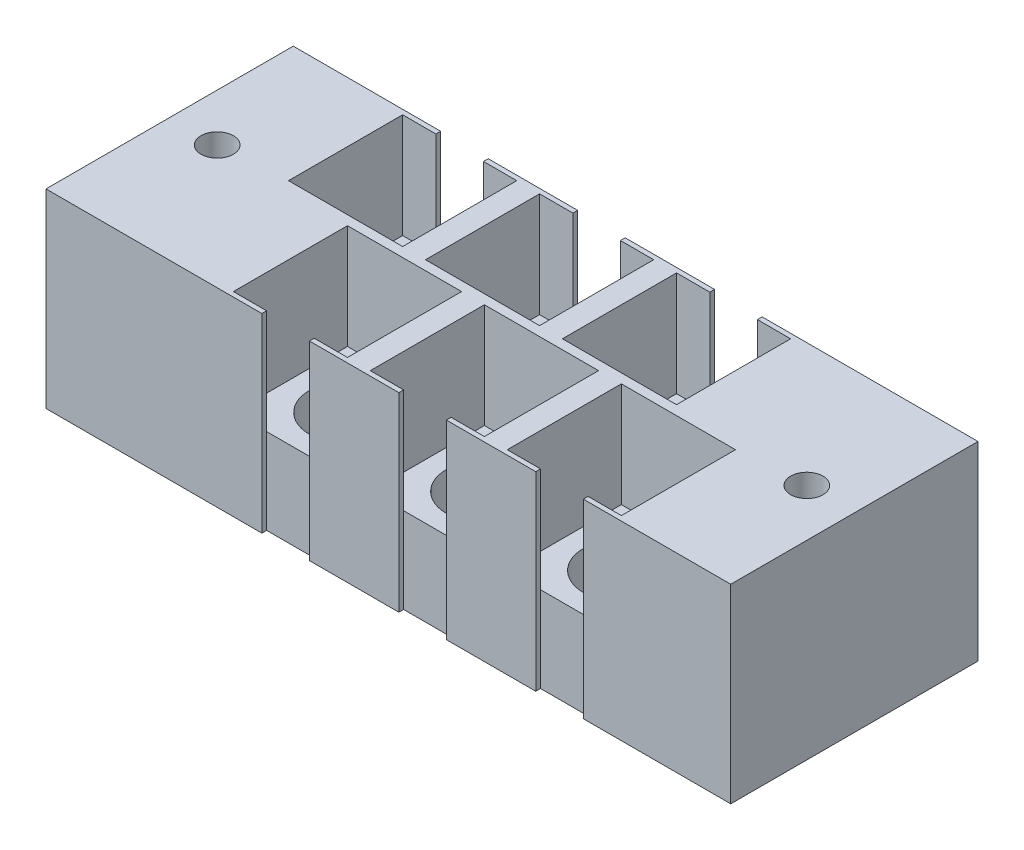
SolidWorks part; units mm, degrees
ref_plane "Front Plane" through (0, 0, 0) normal (0, 0, 1) x (1, 0, 0)
ref_plane "Top Plane" through (0, 0, 0) normal (0, 1, 0) x (1, 0, 0)
ref_plane "Right Plane" through (0, 0, 0) normal (1, 0, 0) x (0, 0, -1)
sketch "Sketch1" plane through (0, 0, 0) normal (0, 1, 0) x (1, 0, 0)
  line L0 (6.1864, -4.1649) -> (7.5864, -4.1649)
  line L1 (21.9864, -4.1649) -> (20.5864, -4.1649)
  line L2 (27.7864, -30.1649) -> (29.1864, -30.1649)
  line L3 (13.3864, -30.1649) -> (14.7864, -30.1649)
  line L4 (-6.8136, -4.1649) -> (-18.3136, -4.1649)
  line L5 (-18.3136, -4.1649) -> (-18.3136, -30.1649)
  line L6 (-18.3136, -30.1649) -> (0.3864, -30.1649)
  line L7 (42.1864, -30.1649) -> (53.6864, -30.1649)
  line L8 (53.6864, -30.1649) -> (53.6864, -4.1649)
  line L9 (53.6864, -4.1649) -> (34.9864, -4.1649)
  line L10 (-18.3136, -17.1649) -> (53.6864, -17.1649) construction
  line L11 (48.6864, -4.1649) -> (48.6864, -30.1649) construction
  line L12 (-13.3136, -4.1649) -> (-13.3136, -30.1649) construction
  circle A0 centre (-13.3136, -17.1649) radius 1.7
  circle A1 centre (48.6864, -17.1649) radius 1.7
  line B0 (34.9864, -17.1649) -> (34.9864, -4.1649)
  line B1 (13.3864, -30.1649) -> (9.3864, -30.1649)
  line B2 (0.8864, -29.6649) -> (12.8864, -29.6649)
  line B3 (13.3864, -30.1649) -> (13.3864, -17.1649)
  line B4 (27.7864, -30.1649) -> (27.7864, -17.1649)
  line B5 (42.1864, -30.1649) -> (42.1864, -17.1649)
  line B6 (0.3864, -17.1649) -> (0.3864, -30.1649)
  line B7 (12.8864, -29.6649) -> (12.8864, -17.6649)
  line B8 (29.1864, -17.1649) -> (29.1864, -30.1649)
  line B9 (21.9864, -4.1649) -> (21.9864, -17.1649)
  line B10 (34.4864, -16.6649) -> (34.4864, -4.6649)
  line B11 (20.0864, -16.6649) -> (20.0864, -4.6649)
  line B12 (6.1864, -17.1649) -> (6.1864, -4.1649)
  line B13 (41.6864, -29.6649) -> (41.6864, -17.6649)
  line B14 (15.2864, -29.6649) -> (27.2864, -29.6649)
  line B15 (29.6864, -17.6649) -> (29.6864, -29.6649)
  line B16 (29.6864, -17.6649) -> (41.6864, -29.6649) construction
  line B17 (15.2864, -17.6649) -> (27.2864, -29.6649) construction
  line B18 (0.8864, -17.6649) -> (12.8864, -29.6649) construction
  line B19 (42.1864, -17.1649) -> (29.1864, -17.1649)
  line B20 (5.6864, -16.6649) -> (5.6864, -4.6649)
  line B21 (15.2864, -17.6649) -> (15.2864, -29.6649)
  line B22 (27.7864, -30.1649) -> (23.7864, -30.1649)
  line B23 (29.1864, -30.1649) -> (33.1864, -30.1649)
  line B24 (42.1864, -30.1649) -> (38.1864, -30.1649)
  line B25 (-6.3136, -10.6649) -> (5.6864, -10.6649) construction
  line B26 (8.0864, -10.6649) -> (20.0864, -10.6649) construction
  line B27 (22.4864, -10.6649) -> (34.4864, -10.6649) construction
  line B28 (0.8864, -23.6649) -> (12.8864, -23.6649) construction
  line B29 (15.2864, -23.6649) -> (27.2864, -23.6649) construction
  line B30 (29.6864, -23.6649) -> (41.6864, -23.6649) construction
  line B31 (-26.4152, -23.6649) -> (52.2342, -23.6649) construction
  line B32 (21.9864, -17.1649) -> (34.9864, -17.1649)
  line B33 (-26.4152, -10.6649) -> (52.2342, -10.6649) construction
  line B34 (28.4864, -16.6649) -> (28.4864, -4.6649) construction
  line B35 (35.6864, -17.6649) -> (35.6864, -29.6649) construction
  line B36 (21.2864, -17.6649) -> (21.2864, -29.6649) construction
  line B37 (14.0864, -16.6649) -> (14.0864, -4.6649) construction
  line B38 (6.8864, -17.6649) -> (6.8864, -29.6649) construction
  line B39 (-0.3136, -16.6649) -> (-0.3136, -4.6649) construction
  line B40 (22.4864, -4.6649) -> (22.4864, -16.6649)
  line B41 (22.4864, -16.6649) -> (34.4864, -16.6649)
  line B42 (34.4864, -4.6649) -> (22.4864, -4.6649)
  line B43 (34.4864, -16.6649) -> (22.4864, -4.6649) construction
  line B44 (34.4864, -4.6649) -> (22.4864, -16.6649) construction
  line B45 (34.9864, -4.1649) -> (30.9864, -4.1649)
  line B46 (21.9864, -4.1649) -> (25.9864, -4.1649)
  line B47 (30.9864, -4.1649) -> (30.9864, -4.6649)
  line B48 (25.9864, -4.1649) -> (25.9864, -4.6649)
  circle B49 centre (28.4864, -10.6649) radius 4
  line B50 (0.8864, -17.6649) -> (0.8864, -29.6649)
  line B51 (12.8864, -17.6649) -> (0.8864, -17.6649)
  line B52 (0.8864, -29.6649) -> (12.8864, -17.6649) construction
  line B53 (13.3864, -17.1649) -> (0.3864, -17.1649)
  line B54 (0.3864, -30.1649) -> (4.3864, -30.1649)
  line B55 (4.3864, -30.1649) -> (4.3864, -29.6649)
  line B56 (9.3864, -30.1649) -> (9.3864, -29.6649)
  circle B57 centre (6.8864, -23.6649) radius 4
  line B58 (27.2864, -29.6649) -> (27.2864, -17.6649)
  line B59 (27.2864, -17.6649) -> (15.2864, -17.6649)
  line B60 (15.2864, -29.6649) -> (27.2864, -17.6649) construction
  line B61 (27.7864, -17.1649) -> (14.7864, -17.1649)
  line B62 (14.7864, -17.1649) -> (14.7864, -30.1649)
  line B63 (14.7864, -30.1649) -> (18.7864, -30.1649)
  line B64 (18.7864, -30.1649) -> (18.7864, -29.6649)
  line B65 (23.7864, -30.1649) -> (23.7864, -29.6649)
  circle B66 centre (21.2864, -23.6649) radius 4
  line B67 (41.6864, -17.6649) -> (29.6864, -17.6649)
  line B68 (29.6864, -29.6649) -> (41.6864, -29.6649)
  line B69 (29.6864, -29.6649) -> (41.6864, -17.6649) construction
  line B70 (33.1864, -30.1649) -> (33.1864, -29.6649)
  line B71 (38.1864, -30.1649) -> (38.1864, -29.6649)
  circle B72 centre (35.6864, -23.6649) radius 4
  line B73 (8.0864, -4.6649) -> (8.0864, -16.6649)
  line B74 (8.0864, -16.6649) -> (20.0864, -16.6649)
  line B75 (20.0864, -4.6649) -> (8.0864, -4.6649)
  line B76 (20.0864, -16.6649) -> (8.0864, -4.6649) construction
  line B77 (20.0864, -4.6649) -> (8.0864, -16.6649) construction
  line B78 (7.5864, -17.1649) -> (20.5864, -17.1649)
  line B79 (20.5864, -17.1649) -> (20.5864, -4.1649)
  line B80 (7.5864, -4.1649) -> (7.5864, -17.1649)
  line B81 (20.5864, -4.1649) -> (16.5864, -4.1649)
  line B82 (7.5864, -4.1649) -> (11.5864, -4.1649)
  line B83 (16.5864, -4.1649) -> (16.5864, -4.6649)
  line B84 (11.5864, -4.1649) -> (11.5864, -4.6649)
  circle B85 centre (14.0864, -10.6649) radius 4
  line B86 (-6.3136, -4.6649) -> (-6.3136, -16.6649)
  line B87 (-6.3136, -16.6649) -> (5.6864, -16.6649)
  line B88 (5.6864, -4.6649) -> (-6.3136, -4.6649)
  line B89 (5.6864, -16.6649) -> (-6.3136, -4.6649) construction
  line B90 (5.6864, -4.6649) -> (-6.3136, -16.6649) construction
  line B91 (-6.8136, -17.1649) -> (6.1864, -17.1649)
  line B92 (-6.8136, -4.1649) -> (-6.8136, -17.1649)
  line B93 (6.1864, -4.1649) -> (2.1864, -4.1649)
  line B94 (-6.8136, -4.1649) -> (-2.8136, -4.1649)
  line B95 (2.1864, -4.1649) -> (2.1864, -4.6649)
  line B96 (-2.8136, -4.1649) -> (-2.8136, -4.6649)
  circle B97 centre (-0.3136, -10.6649) radius 4
  dimension "D5" = 72
  dimension "D1" = 12
  dimension "D2" = 12
  dimension "D3" = 5
  dimension "D4" = 5
  dimension "D6" = 62
  dimension "D7" = 62
sketch_block_instance "Block1-5"
sketch_block "Block1" parameters "D3"=6, "D1"=12, "D2"=12, "D4"=12, "D5"=78.6494, "D6"=78.6494, "D7"=78.6494, "D8"=10.3235, "D9"=14.0261, "D10"=17.7654, "D11"=23.7534, "D12"=22.7743
sketch_block_instance "Block2-2"
sketch_block "Block2" parameters "D1"=12
sketch_block_instance "Block2-3"
sketch_block_instance "Block2-4"
sketch_block_instance "Block2-5"
sketch_block_instance "Block2-6"
sketch_block_instance "Block2-7"
sketch_block_instance "Block3-1"
sketch_block "Block3"
sketch_block_instance "Block4-1"
sketch_block "Block4"
sketch_block_instance "Block5-1"
sketch_block "Block5"
sketch_block_instance "Block6-1"
sketch_block "Block6"
sketch_block_instance "Block7-1"
sketch_block "Block7"
sketch_block_instance "Block8-1"
sketch_block "Block8"
extrude "Boss-Extrude1" add sketch "Sketch1" along normal blind 9 contours B50 B2 B7 B51 B57 | B20 B88 B86 B87 B97 | B11 B75 B73 B74 B85 | B10 B42 B40 B41 B49 | B21 B14 B58 B59 B66 | B15 B68 B13 B67 B72 region at (3.9364, 0, 4.8346) region at (14.0864, 0, 4.8346) region at (2.6364, 0, 29.4952) region at (17.0364, 0, 29.4952) region at (28.4864, 0, 4.8346) region at (31.4364, 0, 29.4952)
extrude "Boss-Extrude2" add sketch "Sketch1<4>" along normal blind 20 contours B92 L4 L5 L6 B6 B91 A0 | B8 B32 B4 L2 | B79 B61 B9 L1 | B78 B3 L3 B62 | B12 B53 B80 L0 | B96 B94 B92 B91 B53 B12 B93 B95 B88 B20 B87 B86 | B56 B1 B3 B53 B6 B54 B55 B2 B50 B51 B7 | B84 B82 B80 B53 B78 B61 B79 B81 B83 B75 B11 B74 B73 | B71 B24 B5 B19 B32 B8 B23 B70 B68 B15 B67 B13 | B48 B46 B9 B32 B0 B45 B47 B42 B10 B41 B40 | B65 B22 B4 B32 B61 B62 B63 B64 B14 B21 B59 B58 | B5 L7 L8 L9 B0 B19 A1 region at (6.8864, 0, 10.6649) region at (6.0025, 0, 10.6649) region at (9.5864, 0, 4.3487) region at (6.8864, 0, 17.3487) region at (-10.2639, 0, 18.7512) region at (14.0864, 0, 23.6649) region at (17.6864, 0, 17.3487) region at (21.2864, 0, 10.6649) region at (22.1702, 0, 10.6649) region at (28.4864, 0, 23.6649) region at (32.0864, 0, 17.3487) region at (45.6367, 0, 15.5785)
sketch "Sketch1<4>" plane through (0, 0, 0) normal (0, 1, 0) x (1, 0, 0) same geometry as "Sketch1"
sketch "Sketch2" plane through (0, 0, 0) normal (0, -1, 0) x (1, 0, 0)
  line L0 (-0.3136, 4.6649) -> (-0.3136, 30.1649) construction
  line L1 (2.1864, 4.6649) -> (-2.8136, 4.6649) construction
  line L2 (-18.3136, 30.1649) -> (4.3864, 30.1649) construction
  line L3 (6.8864, 29.6649) -> (6.8864, 4.1649) construction
  line L4 (4.3864, 29.6649) -> (9.3864, 29.6649) construction
  line L5 (2.1864, 4.1649) -> (11.5864, 4.1649) construction
  line L6 (14.0864, 4.6649) -> (14.0864, 30.1649) construction
  line L7 (16.5864, 4.6649) -> (11.5864, 4.6649) construction
  line L8 (9.3864, 30.1649) -> (18.7864, 30.1649) construction
  line L9 (21.2864, 29.6649) -> (21.2864, 4.1649) construction
  line L10 (18.7864, 29.6649) -> (23.7864, 29.6649) construction
  line L11 (25.9864, 4.1649) -> (16.5864, 4.1649) construction
  line L12 (28.4864, 4.6649) -> (28.4864, 30.1649) construction
  line L13 (30.9864, 4.6649) -> (25.9864, 4.6649) construction
  line L14 (33.1864, 30.1649) -> (23.7864, 30.1649) construction
  line L15 (35.6864, 29.6649) -> (35.6864, 4.1649) construction
  line L16 (33.1864, 29.6649) -> (38.1864, 29.6649) construction
  line L17 (53.6864, 4.1649) -> (30.9864, 4.1649) construction
  line L18 (-0.3136, 17.4149) -> (35.6864, 17.4149) construction
  line L19 (6.8864, 19.6649) -> (-18.3136, 19.6649) construction
  line L20 (-18.3136, 4.1649) -> (-18.3136, 30.1649) construction
  line L21 (-18.3136, 19.6649) -> (53.6864, 19.6649) construction
  line L22 (53.6864, 30.1649) -> (53.6864, 4.1649) construction
  line L23 (-0.3136, 14.6649) -> (-18.3136, 14.6649) construction
  line L24 (-18.3136, 14.6649) -> (53.6864, 14.6649) construction
  line L25 (4.3864, 19.6649) -> (4.3864, 14.6649)
  line L26 (4.3864, 14.6649) -> (2.1864, 14.6649)
  line L27 (2.1864, 14.6649) -> (2.1864, 19.6649)
  line L28 (2.1864, 19.6649) -> (4.3864, 19.6649)
  circle A0 centre (6.8864, 23.6649) radius 4 construction
  circle A1 centre (-0.3136, 10.6649) radius 4 construction
  line B0 (6.8864, 4.6649) -> (6.8864, 30.1649) construction
  line B1 (11.5864, 19.6649) -> (11.5864, 14.6649)
  line B2 (11.5864, 14.6649) -> (9.3864, 14.6649)
  line B3 (9.3864, 14.6649) -> (9.3864, 19.6649)
  line B4 (9.3864, 19.6649) -> (11.5864, 19.6649)
  line B5 (18.7864, 19.6649) -> (18.7864, 14.6649)
  line B6 (18.7864, 14.6649) -> (16.5864, 14.6649)
  line B7 (16.5864, 14.6649) -> (16.5864, 19.6649)
  line B8 (16.5864, 19.6649) -> (18.7864, 19.6649)
  line B9 (25.9864, 19.6649) -> (25.9864, 14.6649)
  line B10 (25.9864, 14.6649) -> (23.7864, 14.6649)
  line B11 (23.7864, 14.6649) -> (23.7864, 19.6649)
  line B12 (23.7864, 19.6649) -> (25.9864, 19.6649)
  line B13 (33.1864, 19.6649) -> (33.1864, 14.6649)
  line B14 (33.1864, 14.6649) -> (30.9864, 14.6649)
  line B15 (30.9864, 14.6649) -> (30.9864, 19.6649)
  line B16 (30.9864, 19.6649) -> (33.1864, 19.6649)
  dimension "D1" = 2.5
  dimension "D2" = 2.5
sketch_block_instance "Block9-1"
sketch_block "Block9"
sketch_block_instance "Block9-2"
sketch_block_instance "Block9-3"
sketch_block_instance "Block9-4"
extrude "Boss-Extrude3" add sketch "Sketch2" along normal blind 4
sketch "Sketch3" plane through (0, 0, 0) normal (0, -1, 0) x (1, 0, 0)
  text T0 "F1"
extrude "Boss-Extrude4" add sketch "Sketch3" against normal blind 1
extrude "Cut-Extrude1" cut sketch "Sketch3<2>" against normal blind 1
sketch "Sketch3<2>" plane through (0, 0, 0) normal (0, -1, 0) x (1, 0, 0) same geometry as "Sketch3"
